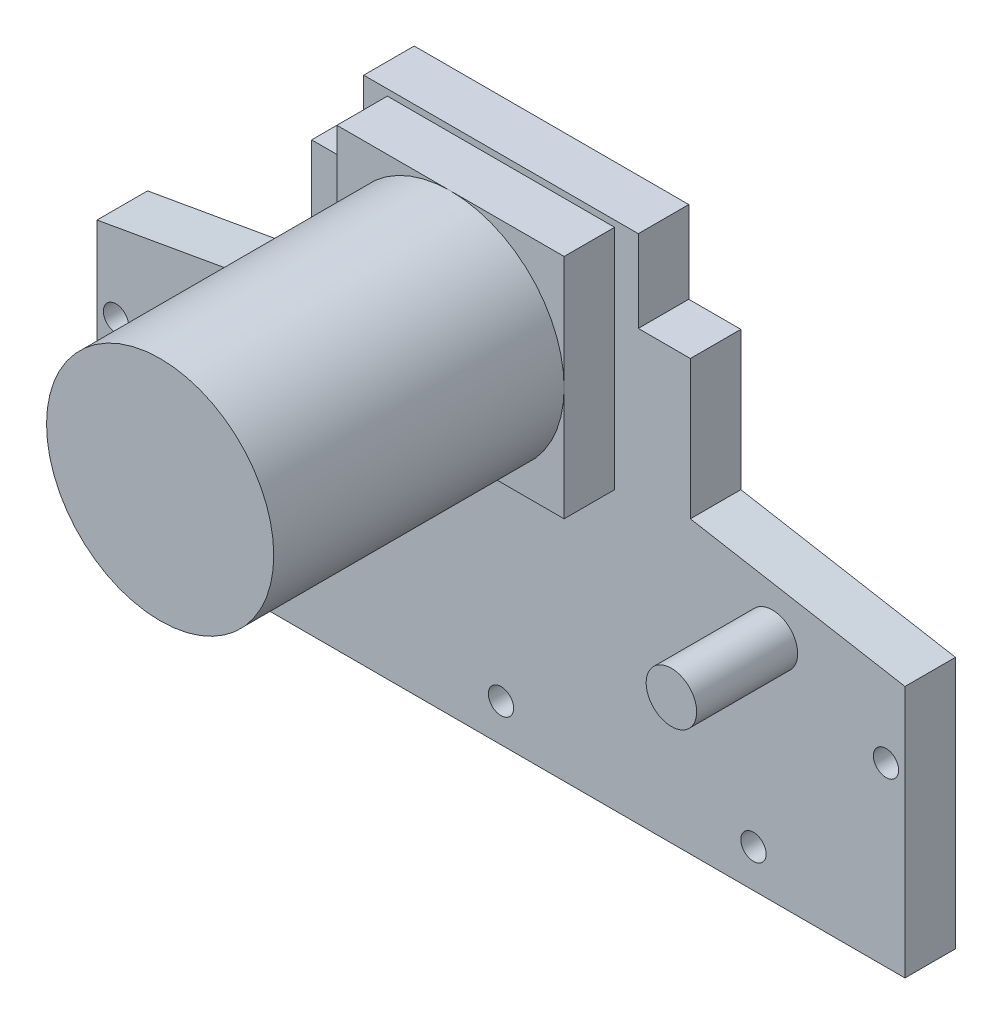
SolidWorks part; units mm, degrees
material "Nickel"
ref_plane "Front Plane" through (0, 0, 0) normal (0, 0, 1) x (1, 0, 0)
ref_plane "Top Plane" through (0, 0, 0) normal (0, 1, 0) x (1, 0, 0)
ref_plane "Right Plane" through (0, 0, 0) normal (1, 0, 0) x (0, 0, -1)
sketch "Sketch1" plane through (0, 0, 0) normal (0, 0, 1) x (1, 0, 0)
  line L0 (-32, 0) -> (32, 0)
  line L1 (-1015.4659, 23) -> (48984.5341, 23) construction
  line L2 (-15, 23) -> (15, 23)
  line L3 (-32, 0) -> (-32, 20)
  line L4 (-32, 20) -> (-15, 23)
  line L5 (32, 0) -> (32, 20)
  line L6 (32, 20) -> (15, 23)
  line L7 (-15, 23) -> (-15, 34)
  line L8 (-15, 34) -> (15, 34)
  line L9 (15, 34) -> (15, 23)
  line L10 (-1006.9308, 40.5) -> (48993.0692, 40.5) construction
  line L11 (-10.875, 40.5) -> (10.875, 40.5)
  line L12 (-10.875, 40.5) -> (-10.875, 34)
  line L13 (10.875, 40.5) -> (10.875, 34)
  line L14 (0, 34) -> (0, 40.5) construction
  dimension "D1" = 64
  dimension "D2" = 23
  dimension "D3" = 30
  dimension "D4" = 20
  dimension "D5" = 11
  dimension "D6" = 6.5
  dimension "D7" = 21.75
extrude "Boss-Extrude1" add sketch "Sketch1" along normal blind 4 contours L5 L6 L2 L4 L3 L0 | L9 L8 L7 L2 | L13 L11 L12 L8 region at (0, 11.1232, 0) region at (0, 28.5, 0) region at (0, 37.25, 0)
sketch "Sketch2" plane through (0, 0, 4) normal (0, 0, 1) x (1, 0, 0)
  line L0 (-1024.4669, 3) -> (48975.5331, 3) construction
  line L1 (-32, 0) -> (32, 0) construction
  line L2 (-20, 3) -> (20, 3)
  line L3 (-32, 0) -> (-32, 20) construction
  line L4 (0, -997) -> (0, 49003) construction
  circle A0 centre (-20, 3) radius 1
  circle A1 centre (20, 3) radius 1
  circle A2 centre (0, 3) radius 1
  circle A3 centre (-30.5, 14) radius 1
  circle A4 centre (30.5, 14) radius 1
  dimension "D3" = 2
  dimension "D1" = 40
  dimension "D2" = 3
  dimension "D5" = 14
  dimension "D6" = 1.5
extrude "Cut-Extrude1" cut sketch "Sketch2" against normal blind 5 contours A3 | A1 | A0 | A2 | A4 region at (20, 3.9717, 4) region at (-30.5, 14, 4)
sketch "Sketch3" plane through (0, 0, 4) normal (0, 0, 1) x (1, 0, 0)
  line L0 (0, 40.5) -> (0, 0) construction
  line L1 (-10.875, 40.5) -> (10.875, 40.5) construction
  line L2 (-32, 0) -> (32, 0) construction
  line L4 (-8.5, 39.5) -> (8.5, 39.5)
  line L5 (-8.5, 39.5) -> (-8.5, 22.5)
  line L6 (-8.5, 22.5) -> (8.5, 22.5)
  line L7 (8.5, 39.5) -> (8.5, 22.5)
  circle A0 centre (0, 31) radius 9
  circle A1 centre (0, 31) radius 8.5
  dimension "D1" = 18
  dimension "D2" = 17
  dimension "D3" = 17
  dimension "D4" = 1
extrude "Boss-Extrude2" add sketch "Sketch3" along normal blind 27 contours A0
sketch "Sketch4" plane through (0, 0, 31) normal (0, 0, 1) x (1, 0, 0)
  circle A0 centre (0, 31) radius 9
sketch "Sketch5" plane through (0, 0, 0) normal (0, 0, -1) x (-1, 0, 0)
  line L0 (32, 0) -> (-32, 0) construction
  line L1 (-5, 10) -> (13, 10)
  line L2 (-5, 10) -> (-5, 28)
  line L3 (-5, 28) -> (13, 28)
  line L4 (13, 10) -> (13, 28)
  line L5 (32, 0) -> (32, 20) construction
  line L6 (15, 23) -> (15, 34) construction
  dimension "D1" = 28
  dimension "D2" = 19
  dimension "D3" = 20
  dimension "D4" = 10
extrude "Boss-Extrude3" add sketch "Sketch5" along normal blind 3
sketch "Sketch6" plane through (0, 0, 4) normal (0, 0, 1) x (1, 0, 0)
  line L0 (21.5, 18) -> (-21.5, 18) construction
  line L1 (0, 0) -> (0, 18) construction
  line L2 (-32, 0) -> (32, 0) construction
  circle A0 centre (21.5, 18) radius 2
  circle A1 centre (-21.5, 18) radius 2
  dimension "D2" = 4
  dimension "D1" = 43
  dimension "D3" = 18
extrude "Boss-Extrude4" add sketch "Sketch6" along normal blind 8
sketch "Sketch7" plane through (0, 0, 4) normal (0, 0, 1) x (1, 0, 0)
  line L1 (-9, 40) -> (9, 40)
  line L2 (-9, 40) -> (-9, 22)
  line L3 (-9, 22) -> (9, 22)
  line L4 (9, 40) -> (9, 22)
  line L5 (-9, 40) -> (9, 22) construction
  line L6 (-9, 22) -> (9, 40) construction
  circle A0 centre (0, 31) radius 9 construction
  circle A1 centre (0, 31) radius 9 construction
  point P0 (0, 31)
extrude "Boss-Extrude5" add sketch "Sketch7" along normal blind 4
